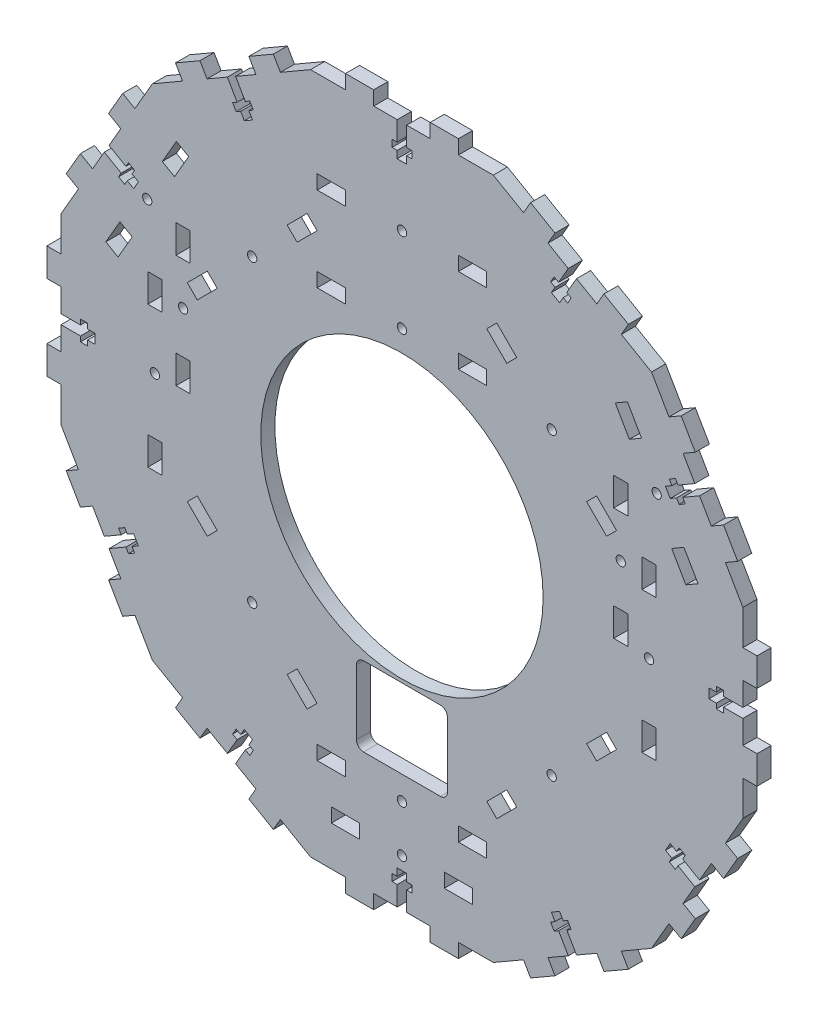
SolidWorks part; units mm, degrees
ref_plane "Front Plane" through (0, 0, 0) normal (0, 0, 1) x (1, 0, 0)
ref_plane "Top Plane" through (0, 0, 0) normal (0, 1, 0) x (1, 0, 0)
ref_plane "Right Plane" through (0, 0, 0) normal (1, 0, 0) x (0, 0, -1)
sketch "Sketch1" plane through (0, 0, 0) normal (0, 0, 1) x (1, 0, 0)
  line L1 (41.0875, 153.3407) -> (-41.0875, 153.3407)
  line L2 (-41.0875, 153.3407) -> (-112.2532, 112.2532)
  line L3 (-112.2532, 112.2532) -> (-153.3407, 41.0875)
  line L4 (-153.3407, 41.0875) -> (-153.3407, -41.0875)
  line L5 (-153.3407, -41.0875) -> (-112.2532, -112.2532)
  line L6 (-112.2532, -112.2532) -> (-41.0875, -153.3407)
  line L7 (-41.0875, -153.3407) -> (41.0875, -153.3407)
  line L8 (41.0875, -153.3407) -> (112.2532, -112.2532)
  line L9 (112.2532, -112.2532) -> (153.3407, -41.0875)
  line L10 (153.3407, -41.0875) -> (153.3407, 41.0875)
  line L11 (153.3407, 41.0875) -> (112.2532, 112.2532)
  line L12 (112.2532, 112.2532) -> (41.0875, 153.3407)
  circle A0 centre (0, 0) radius 158.75 construction
  dimension "D1" = 317.5
extrude "Boss-Extrude1" add sketch "Sketch1" along normal blind 6.35
sketch "Sketch2" plane through (0, 0, 6.35) normal (0, 0, 1) x (1, 0, 0)
  line L0 (41.0875, 153.3407) -> (-41.0875, 153.3407) construction
  line L1 (-25.4, 153.3407) -> (-12.7, 153.3407)
  line L2 (-25.4, 153.3407) -> (-25.4, 159.6907)
  line L3 (-25.4, 159.6907) -> (-12.7, 159.6907)
  line L4 (-12.7, 153.3407) -> (-12.7, 159.6907)
  line L5 (0, 153.3407) -> (0, 105.1769) construction
  line L6 (2.1336, 153.3407) -> (-2.1336, 153.3407)
  line L7 (-2.1336, 141.4027) -> (-4.445, 141.4027)
  line L8 (-4.445, 141.4027) -> (-4.445, 144.5777)
  line L9 (-4.445, 144.5777) -> (-2.1336, 144.5777)
  line L10 (-2.1336, 144.5777) -> (-2.1336, 153.3407)
  line L11 (-2.1336, 141.4027) -> (-2.1336, 138.1007)
  line L12 (-2.1336, 138.1007) -> (2.1336, 138.1007)
  line L13 (2.1336, 141.4027) -> (2.1336, 138.1007)
  line L14 (2.1336, 144.5777) -> (2.1336, 153.3407)
  line L15 (4.445, 144.5777) -> (2.1336, 144.5777)
  line L16 (4.445, 141.4027) -> (4.445, 144.5777)
  line L17 (2.1336, 141.4027) -> (4.445, 141.4027)
  line L18 (12.7, 153.3407) -> (12.7, 159.6907)
  line L19 (25.4, 159.6907) -> (12.7, 159.6907)
  line L20 (25.4, 153.3407) -> (25.4, 159.6907)
  line L21 (25.4, 153.3407) -> (12.7, 153.3407)
  point P18 (0, 138.1007)
  line M2 (41.0875, 153.3407) -> (-41.0875, 153.3407)
  dimension "D1" = 12.7
  dimension "D2" = 12.7
  dimension "D3" = 6.35
  dimension "D4" = 2.1336
  dimension "D5" = 21.59
  dimension "D6" = 3.302
  dimension "D7" = 3.175
  dimension "D8" = 4.445
extrude "Boss-Extrude2" add sketch "Sketch2" against normal blind 6.35 contours L4 L3 L2 M2 | L20 L19 L18 M2 region at (-19.05, 156.5157, 6.35) region at (19.05, 156.5157, 6.35)
extrude "Cut-Extrude1" cut sketch "Sketch2<3>" against normal blind 6.35 contours L5 L6 L10 L9 L8 L7 L11 L12 | L5 L12 L13 L17 L16 L15 L14 M2 region at (-1.476, 145.2179, 6.35) region at (1.476, 145.2179, 6.35)
sketch "Sketch2<3>" plane through (0, 0, 6.35) normal (0, 0, 1) x (1, 0, 0) same geometry as "Sketch2"
ref_axis "Axis1" through (0, 0, 0) along (0, 0, 1)
pattern_circular "CirPattern1" count 12 every 30 about axis through (0, 0, 0) along (0, 0, 1) of "Boss-Extrude2", "Cut-Extrude1"
sketch "Sketch5" plane through (0, 0, 6.35) normal (0, 0, 1) x (1, 0, 0)
  circle A0 centre (0, 0) radius 63.5
  dimension "D1" = 127
extrude "Cut-Extrude2" cut sketch "Sketch5" against normal blind 6.35
sketch "Sketch7" plane through (0, 0, 6.35) normal (0, 0, 1) x (1, 0, 0)
  line L0 (-19.05, -132.2751) -> (19.05, -132.2751) construction
  line L2 (19.05, -135.4501) -> (19.05, -129.1001) construction
  line L20 (-31.75, -129.1001) -> (-19.05, -129.1001)
  line L21 (-31.75, -129.1001) -> (-31.75, -135.4501)
  line L22 (-31.75, -135.4501) -> (-19.05, -135.4501)
  line L23 (-19.05, -129.1001) -> (-19.05, -135.4501)
  line L24 (19.05, -129.1001) -> (31.75, -129.1001)
  line L25 (19.05, -129.1001) -> (19.05, -135.4501)
  line L26 (19.05, -135.4501) -> (31.75, -135.4501)
  line L27 (31.75, -129.1001) -> (31.75, -135.4501)
  circle A0 centre (0, -132.2751) radius 2.0955
  dimension "D1" = 4.191
extrude "Cut-Extrude3" cut sketch "Sketch7" against normal blind 6.35
sketch "Sketch8" plane through (0, 0, 6.35) normal (0, 0, 1) x (1, 0, 0)
  line L0 (98.425, 50.8) -> (98.425, 12.7) construction
  line L1 (95.25, 50.8) -> (101.6, 50.8)
  line L2 (95.25, 50.8) -> (95.25, 63.5)
  line L3 (95.25, 63.5) -> (101.6, 63.5)
  line L4 (101.6, 50.8) -> (101.6, 63.5)
  line L5 (95.25, 0) -> (101.6, 0)
  line L6 (95.25, 0) -> (95.25, 12.7)
  line L7 (95.25, 12.7) -> (101.6, 12.7)
  line L8 (101.6, 0) -> (101.6, 12.7)
  circle A0 centre (98.425, 31.75) radius 2.0955
  dimension "D1" = 4.191
extrude "Cut-Extrude4" cut sketch "Sketch8" against normal blind 6.35
pattern_circular "CirPattern2" count 3 every 120 about axis through (0, 0, 0) along (0, 0, 1) of "Cut-Extrude3"
mirror "Mirror1" about plane through (0, 0, 0) normal (1, 0, 0) of "Cut-Extrude4"
sketch "Sketch9" plane through (0, 0, 6.35) normal (0, 0, 1) x (1, 0, 0)
  line L0 (0, 0) -> (0, -111.125) construction
  line L1 (0, -111.125) -> (-25.4, -111.125) construction
  line L2 (25.4, -114.3) -> (38.1, -107.95) construction
  line L3 (-25.4, -107.95) -> (-38.1, -107.95)
  line L4 (-25.4, -107.95) -> (-25.4, -114.3)
  line L5 (-25.4, -114.3) -> (-38.1, -114.3)
  line L6 (-38.1, -107.95) -> (-38.1, -114.3)
  line L7 (-25.4, -107.95) -> (-38.1, -114.3) construction
  line L8 (-25.4, -114.3) -> (-38.1, -107.95) construction
  line L9 (25.4, -107.95) -> (38.1, -114.3) construction
  line L10 (38.1, -107.95) -> (38.1, -114.3)
  line L11 (25.4, -114.3) -> (38.1, -114.3)
  line L12 (25.4, -107.95) -> (25.4, -114.3)
  line L13 (25.4, -107.95) -> (38.1, -107.95)
  circle A0 centre (0, -111.125) radius 2.0955
  point P4 (-31.75, -111.125)
  point P14 (31.75, -111.125)
  dimension "D5" = 4.191
  dimension "D1" = 111.125
  dimension "D2" = 25.4
  dimension "D3" = 12.7
  dimension "D4" = 6.35
extrude "Cut-Extrude5" cut sketch "Sketch9" against normal blind 6.35
sketch "Sketch10" plane through (0, 0, 6.35) normal (0, 0, 1) x (1, 0, 0)
  line L0 (67.3519, 67.3519) -> (40.4112, 94.2927) construction
  line L1 (0, 0) -> (28.5864, 0) construction
  line L2 (0, 0) -> (67.3519, 67.3519) construction
  line L3 (47.1463, 83.0674) -> (38.1661, 92.0476)
  line L4 (47.1463, 83.0674) -> (51.6365, 87.5575)
  line L5 (38.1661, 92.0476) -> (42.6562, 96.5378)
  line L6 (51.6365, 87.5575) -> (42.6562, 96.5378)
  line L7 (47.1463, 83.0674) -> (42.6562, 96.5378) construction
  line L8 (38.1661, 92.0476) -> (51.6365, 87.5575) construction
  line L11 (92.0476, 38.1661) -> (96.5378, 42.6562)
  line L12 (87.5575, 51.6365) -> (96.5378, 42.6562)
  line L13 (83.0674, 47.1463) -> (92.0476, 38.1661)
  line L14 (83.0674, 47.1463) -> (87.5575, 51.6365)
  line L15 (38.1, -114.3) -> (38.1, -107.95) construction
  line L16 (38.1, -107.95) -> (25.4, -107.95) construction
  circle A0 centre (67.3519, 67.3519) radius 2.0955
  circle A2 centre (0, -111.125) radius 2.0955 construction
  point P10 (44.9013, 89.8026)
  dimension "D1" = 45
  dimension "D2" = 95.25
  dimension "D3" = 38.1
extrude "Cut-Extrude6" cut sketch "Sketch10" against normal up to next
pattern_circular "CirPattern3" count 4 every 90 about axis through (0, 0, 0) along (0, 0, 1) of "Cut-Extrude5", "Cut-Extrude6"
sketch "Sketch11" plane through (0, 0, 6.35) normal (0, 0, 1) x (1, 0, 0)
  line L0 (-20.447, -64.9651) -> (-20.447, -100.5251)
  line L1 (-17.272, -68.1401) -> (17.272, -68.1401) construction
  line L2 (-17.272, -68.1401) -> (-17.272, -97.3501) construction
  line L3 (-17.272, -97.3501) -> (17.272, -97.3501) construction
  line L4 (17.272, -68.1401) -> (17.272, -97.3501) construction
  line L5 (-20.447, -100.5251) -> (20.447, -100.5251)
  line L6 (20.447, -64.9651) -> (20.447, -100.5251)
  line L7 (-20.447, -64.9651) -> (20.447, -64.9651)
  dimension "D1" = 3.175
extrude "Cut-Extrude7" cut sketch "Sketch11" against normal up to next
fillet "Fillet1" radius 3.175 4 edges at (-20.447, -64.9651, 3.175) (-20.447, -100.5251, 3.175) (20.447, -100.5251, 3.175) (20.447, -64.9651, 3.175)
sketch "Sketch12" plane through (0, 0, 6.35) normal (0, 0, 1) x (1, 0, 0)
  line L0 (0, 111.125) -> (0, 0) construction
  line L1 (0, 73.025) -> (-25.4, 73.025) construction
  line L2 (-38.1, 76.2) -> (-25.4, 76.2)
  line L3 (-38.1, 76.2) -> (-38.1, 69.85)
  line L4 (-38.1, 69.85) -> (-25.4, 69.85)
  line L5 (-25.4, 76.2) -> (-25.4, 69.85)
  line L6 (-38.1, 107.95) -> (-25.4, 107.95) construction
  line L7 (-38.1, 114.3) -> (-38.1, 107.95) construction
  line L8 (25.4, 76.2) -> (25.4, 69.85)
  line L9 (38.1, 76.2) -> (38.1, 69.85)
  line L10 (38.1, 76.2) -> (25.4, 76.2)
  line L11 (38.1, 69.85) -> (25.4, 69.85)
  circle A1 centre (0, 73.025) radius 2.0955
  circle A2 centre (0, 111.125) radius 2.0955 construction
  dimension "D1" = 25.4
  dimension "D2" = 73.025
extrude "Cut-Extrude8" cut sketch "Sketch12" against normal up to next
